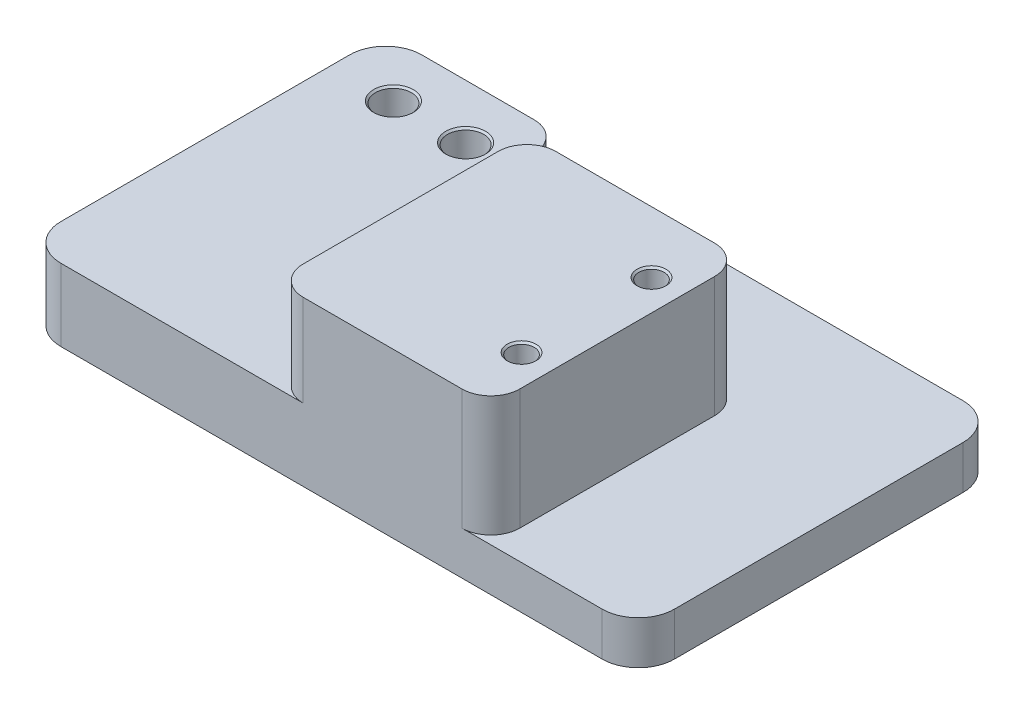
SolidWorks part; units mm, degrees
ref_plane "Front Plane" through (0, 0, 0) normal (0, 0, 1) x (1, 0, 0)
ref_plane "Top Plane" through (0, 0, 0) normal (0, 1, 0) x (1, 0, 0)
ref_plane "Right Plane" through (0, 0, 0) normal (1, 0, 0) x (0, 0, -1)
sketch "Sketch1" plane through (0, 0, 0) normal (0, 1, 0) x (1, 0, 0)
  line L1 (0, 0) -> (85, 0)
  line L2 (0, 0) -> (0, 50)
  line L3 (0, 50) -> (85, 50)
  line L4 (85, 0) -> (85, 50)
extrude "Boss-Extrude1" add sketch "Sketch1" along normal blind 6
sketch "Sketch2" plane through (0, 6, 0) normal (0, 1, 0) x (1, 0, 0)
  line L1 (85, 50) -> (0, 50) construction
  line L5 (0, 0) -> (85, 0) construction
  line L8 (0, 0) -> (0, 50)
  line L9 (0, 50) -> (24.5743, 50)
  line L10 (24.5743, 50) -> (24.5743, 35)
  line L11 (24.5743, 35) -> (9.5743, 35)
  line L12 (9.5743, 35) -> (9.5743, 0)
  line L13 (9.5743, 0) -> (0, 0)
extrude "Boss-Extrude2" add sketch "Sketch2" along normal blind 4
sketch "Sketch4" plane through (0, 10, 0) normal (0, 1, 0) x (1, 0, 0)
  line L0 (24.5743, 42.5) -> (18.5743, 42.5) construction
  line L1 (24.5743, 35) -> (24.5743, 50) construction
  line L2 (18.5743, 42.5) -> (8.5743, 42.5) construction
  circle A0 centre (18.5743, 42.5) radius 2.5
  circle A1 centre (8.5743, 42.5) radius 2.5
  dimension "D1" = 10
extrude "Cut-Extrude2" cut sketch "Sketch4" against normal blind 11
sketch "Sketch5" plane through (0, 6, 0) normal (0, 1, 0) x (1, 0, 0)
  line L1 (9.5743, 35) -> (9.5743, 0)
  line L5 (9.5743, 0) -> (64.5743, 0)
  line L6 (9.5743, 0) -> (85, 0) construction
  line L7 (64.5743, 0) -> (64.5743, 35)
  line L8 (64.5743, 35) -> (9.5743, 35)
extrude "Boss-Extrude3" add sketch "Sketch5" along normal blind 16.7
fillet "Fillet1" radius 5 4 edges at (85, 3, -50) (85, 3, 0) (0, 5, -50) (0, 5, 0)
sketch "Sketch6" plane through (0, 22.7, 0) normal (0, 1, 0) x (1, 0, 0)
  line L0 (64.5743, 17.5) -> (60.3243, 17.5) construction
  line L1 (64.5743, 0) -> (64.5743, 35) construction
  line L2 (60.3243, 17.5) -> (60.3243, 26.5) construction
  circle A0 centre (60.3243, 26.5) radius 1.75
  circle A1 centre (60.3243, 8.5) radius 1.75
extrude "Cut-Extrude3" cut sketch "Sketch6" against normal blind 10
sketch "Sketch7" plane through (0, 22.7, 0) normal (0, 1, 0) x (1, 0, 0)
  line L0 (9.5743, 35) -> (34.5743, 35)
  line L1 (64.5743, 35) -> (9.5743, 35) construction
  line L2 (34.5743, 35) -> (34.5743, 0)
  line L3 (9.5743, 0) -> (64.5743, 0) construction
  line L4 (34.5743, 0) -> (9.5743, 0)
  line L5 (9.5743, 0) -> (9.5743, 35)
extrude "Cut-Extrude4" cut sketch "Sketch7" against normal up to surface (12.7 mm away) up to face at (18.5743, 10, -40)
fillet "Fillet3" radius 4 4 edges at (64.5743, 14.35, 0) (64.5743, 14.35, -35) (34.5743, 16.35, -35) (34.5743, 16.35, 0)
fillet "Fillet4" radius 4 1 edges at (24.5743, 8, -35)
fillet "Fillet5" radius 4 1 edges at (24.5743, 8, -50)
chamfer "Chamfer1" distance 0.25 angle 45 4 edges at (60.3243, 22.7, -10.25) (60.3243, 22.7, -24.75) (8.5743, 10, -40) (18.5743, 10, -40)
